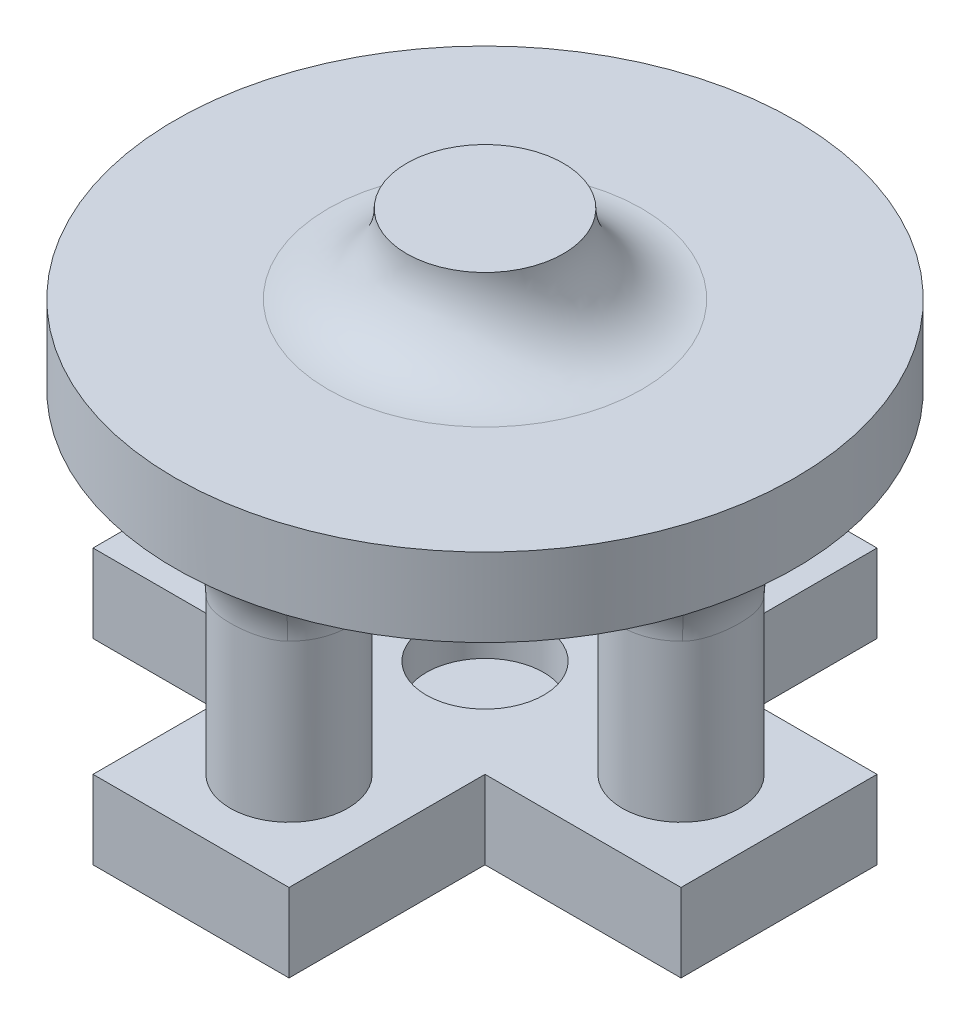
SolidWorks part; units mm, degrees
ref_plane "Front Plane" through (0, 0, 0) normal (0, 0, 1) x (1, 0, 0)
ref_plane "Top Plane" through (0, 0, 0) normal (0, 1, 0) x (1, 0, 0)
ref_plane "Right Plane" through (0, 0, 0) normal (1, 0, 0) x (0, 0, -1)
sketch "Sketch1" plane through (0, 0, 0) normal (0, 1, 0) x (1, 0, 0)
  line L0 (-8.3487, -10.4521) -> (-8.3487, -4.1021)
  line L1 (-8.3487, -4.1021) -> (-1.9987, -4.1021)
  line L2 (-1.9987, -4.1021) -> (-1.9987, -10.4521)
  line L3 (-1.9987, -10.4521) -> (4.3513, -10.4521)
  line L4 (4.3513, -10.4521) -> (4.3513, -16.8021)
  line L5 (4.3513, -16.8021) -> (-1.9987, -16.8021)
  line L6 (-1.9987, -16.8021) -> (-1.9987, -23.1521)
  line L7 (-1.9987, -23.1521) -> (-8.3487, -23.1521)
  line L8 (-8.3487, -23.1521) -> (-8.3487, -16.8021)
  line L9 (-8.3487, -16.8021) -> (-14.6987, -16.8021)
  line L10 (-14.6987, -16.8021) -> (-14.6987, -10.4521)
  line L11 (-14.6987, -10.4521) -> (-8.3487, -10.4521)
  dimension "D1" = 6.35
  dimension "D2" = 6.35
  dimension "D3" = 6.35
  dimension "D4" = 6.35
  dimension "D5" = 6.35
  dimension "D6" = 6.35
  dimension "D7" = 6.35
  dimension "D8" = 6.35
  dimension "D9" = 6.35
  dimension "D10" = 6.35
extrude "body" add sketch "Sketch1" along normal blind 2.54
sketch "Sketch2" plane through (0, 2.54, 0) normal (0, 1, 0) x (1, 0, 0)
  line L0 (-8.3487, -10.4521) -> (-14.6987, -10.4521) construction
  line L1 (-1.9987, -23.1521) -> (-1.9987, -16.8021) construction
  line L2 (-1.9987, -16.8021) -> (4.3513, -16.8021) construction
  line L3 (-1.9987, -10.4521) -> (-1.9987, -4.1021) construction
  line L4 (-1.9987, -4.1021) -> (-8.3487, -4.1021) construction
  line L5 (-14.6987, -10.4521) -> (-14.6987, -16.8021) construction
  line L6 (-8.3487, -23.1521) -> (-1.9987, -23.1521) construction
  line L7 (4.3513, -16.8021) -> (4.3513, -10.4521) construction
  circle A0 centre (-5.1737, -7.2771) radius 1.905
  circle A1 centre (1.1763, -13.6271) radius 1.905
  circle A2 centre (-5.1737, -19.9771) radius 1.905
  circle A3 centre (-11.5237, -13.6271) radius 1.905
  dimension "D1" = 3.81
  dimension "D2" = 3.81
  dimension "D3" = 3.81
  dimension "D4" = 3.81
  dimension "D5" = 3.175
  dimension "D6" = 3.175
  dimension "D7" = 3.175
  dimension "D8" = 3.175
  dimension "D9" = 3.175
  dimension "D10" = 3.175
  dimension "D11" = 3.175
  dimension "D12" = 3.175
extrude "legs" add sketch "Sketch2" along normal blind 7.62
sketch "Sketch4" plane through (0, 2.54, 0) normal (0, 1, 0) x (1, 0, 0)
  line L0 (-8.3487, -23.1521) -> (-1.9987, -23.1521) construction
  line L3 (-1.9987, -4.1021) -> (-8.3487, -4.1021) construction
  circle A0 centre (-5.1737, -13.6271) radius 1.905
  point P10 (-5.1737, -4.1021)
  point P14 (-5.1737, -23.1521)
  dimension "D1" = 3.81
  dimension "D2" = 9.525
  dimension "D3" = 0
extrude "spring hole" cut sketch "Sketch4" against normal blind 1.27
ref_point "centre of flag base"
sketch "Sketch5" plane through (0, 10.16, 0) normal (0, 1, 0) x (1, 0, 0)
  circle A0 centre (-5.1737, -13.6271) radius 10.0402
extrude "foot" add sketch "Sketch5" along normal blind 2.54
sketch "Sketch6" plane through (0, 12.7, 0) normal (0, 1, 0) x (1, 0, 0)
  circle A0 centre (-5.1737, -13.6271) radius 2.54
extrude "flag" add sketch "Sketch6" along normal blind 2.54
ref_point "centre of flag top"
fillet "roundity" radius 2.54 5 edges at (-5.1737, 10.16, 21.8821) (1.1763, 10.16, 15.5321) (-11.5237, 10.16, 15.5321) (-5.1737, 10.16, 9.1821) (-5.1737, 12.7, 16.1671)
